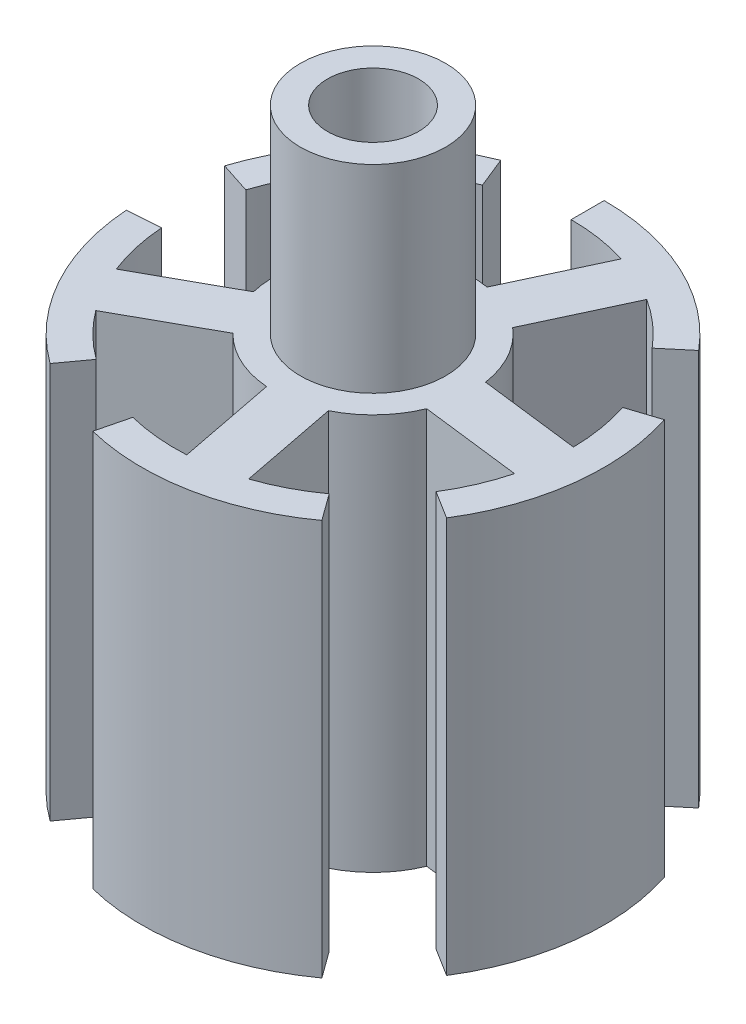
SolidWorks part; units mm, degrees
ref_plane "Front Plane" through (0, 0, 0) normal (0, 0, 1) x (1, 0, 0)
ref_plane "Top Plane" through (0, 0, 0) normal (0, 1, 0) x (1, 0, 0)
ref_plane "Right Plane" through (0, 0, 0) normal (1, 0, 0) x (0, 0, -1)
sketch "Sketch1" plane through (0, 0, 0) normal (0, 1, 0) x (1, 0, 0)
  line L0 (0, 17.5) -> (0, 15)
  line L1 (11.4907, 9.6418) -> (13.4058, 11.2488)
  line L2 (16.6435, 5.4078) -> (14.2658, 4.6353)
  line L3 (12.7207, -7.9488) -> (14.8408, -9.2736)
  line L4 (10.2862, -14.1578) -> (8.8168, -12.1353)
  line L5 (-3.6288, -14.5544) -> (-4.2336, -16.9802)
  line L6 (-10.2862, -14.1578) -> (-8.8168, -12.1353)
  line L7 (-14.9635, -1.0463) -> (-17.4574, -1.2207)
  line L8 (-16.6435, 5.4078) -> (-14.2658, 4.6353)
  line L9 (-5.6191, 13.9078) -> (-6.5556, 16.2257)
  arc A0 (0, 17.5) -> (13.4058, 11.2488) centre (0, 0) cw
  arc A1 (11.4907, 9.6418) -> (0, 15) centre (0, 0) ccw
  arc A2 (16.6435, 5.4078) -> (14.8408, -9.2736) centre (0, 0) cw
  arc A3 (12.7207, -7.9488) -> (14.2658, 4.6353) centre (0, 0) ccw
  arc A4 (10.2862, -14.1578) -> (-4.2336, -16.9802) centre (0, 0) cw
  arc A5 (-3.6288, -14.5544) -> (8.8168, -12.1353) centre (0, 0) ccw
  arc A6 (-10.2862, -14.1578) -> (-17.4574, -1.2207) centre (0, 0) cw
  arc A7 (-14.9635, -1.0463) -> (-8.8168, -12.1353) centre (0, 0) ccw
  arc A8 (-16.6435, 5.4078) -> (-6.5556, 16.2257) centre (0, 0) cw
  arc A9 (-5.6191, 13.9078) -> (-14.2658, 4.6353) centre (0, 0) ccw
  point P25 (0, 0)
  dimension "D1" = 5
extrude "Boss-Extrude2" add sketch "Sketch1" along normal blind 30
sketch "Sketch2" plane through (0, 0, 0) normal (0, 1, 0) x (1, 0, 0)
  line L0 (8.1519, 12.7494) -> (4.5267, 14.4399)
  line L1 (8.1519, 12.7494) -> (1.8723, -0.7172)
  line L2 (4.5267, 14.4399) -> (-1.7529, 0.9732)
  line L3 (1.8723, -0.7172) -> (-1.7529, 0.9732)
  line L4 (14.6445, -3.8131) -> (15.1319, 0.1571)
  line L5 (14.6445, -3.8131) -> (-0.1036, -2.0023)
  line L6 (15.1319, 0.1571) -> (0.3839, 1.9679)
  line L7 (-0.1036, -2.0023) -> (0.3839, 1.9679)
  line L8 (0.8989, -15.106) -> (4.8254, -14.3428)
  line L9 (0.8989, -15.106) -> (-1.9363, -0.5203)
  line L10 (4.8254, -14.3428) -> (1.9902, 0.243)
  line L11 (-1.9363, -0.5203) -> (1.9902, 0.243)
  line L12 (-14.0889, -5.5229) -> (-12.1497, -9.0214)
  line L13 (-14.0889, -5.5229) -> (-1.0931, 1.6808)
  line L14 (-12.1497, -9.0214) -> (0.8461, -1.8177)
  line L15 (-1.0931, 1.6808) -> (0.8461, -1.8177)
  line L16 (-9.6063, 11.6927) -> (-12.3343, 8.7673)
  line L17 (-9.6063, 11.6927) -> (1.2607, 1.559)
  line L18 (-12.3343, 8.7673) -> (-1.4673, -1.3664)
  line L19 (1.2607, 1.559) -> (-1.4673, -1.3664)
  arc A0 (11.4907, 9.6418) -> (0, 15) centre (0, 0) ccw construction
  point P8 (6.3393, 13.5946)
  point P27 (0, 0)
  dimension "D1" = 5
extrude "Boss-Extrude3" add sketch "Sketch2" along normal blind 30 contours L2 L17 L6 L1 L0 | L16 L18 L13 L2 L17 | L18 L13 L12 L14 L9 | L14 L9 L8 L10 L5 | L10 L5 L4 L6 L1 | L7 L15 L14 L5 L10 L1 L3 L11 | L19 L17 L6 L7 | L17 L19 L7 L3 L11 L10 L1 L6 | L19 L7 L6 L17 L2 L13 L15 L3 | L15 L13 L2 L3 | L11 L3 L1 L10 | L11 L19 L18 L9 L14 L5 L7 L15 | L19 L15 L3 L2 L13 L18 L9 L11 | L19 L11 L9 L18 | L15 L7 L5 L14 | L7 L6 L4 L5 | L2 L3 L1 L0 | L15 L14 L12 L13 region at (3.6821, 0, -7.8962) region at (8.6476, 0, 1.0618) region at (1.5876, 0, -0.88) region at (-0.3464, 0, -1.7818) region at (-6.3719, 0, -5.9419) region at (1.3275, 0, 1.2379) region at (1.4907, 0, 0.183) region at (0.6347, 0, -1.3612) region at (-1.0984, 0, -1.0243) region at (-1.8016, 0, -0.2212) region at (1.6624, 0, 8.5524) region at (-7.6201, 0, 4.2239) region at (-0.7671, 0, 1.6451) region at (0.2866, 0, 1.4743) region at (-1.3136, 0, 0.7281)
sketch "Sketch3" plane through (0, 0, 0) normal (0, 1, 0) x (1, 0, 0)
  circle A0 centre (0, 0) radius 7.5
extrude "Boss-Extrude4" add sketch "Sketch3" along normal blind 30
ref_plane "Plane2" through (0, 30, 0) normal (0, 1, 0) x (1, 0, 0)
sketch "Sketch5" plane through (0, 30, 0) normal (0, 1, 0) x (1, 0, 0)
  circle A0 centre (0, 0) radius 5.5
extrude "Boss-Extrude5" add sketch "Sketch5" along normal blind 15
sketch "Sketch4" plane through (0, 0, 0) normal (0, 1, 0) x (1, 0, 0)
  circle A0 centre (0, 0) radius 3.45
extrude "Cut-Extrude1" cut sketch "Sketch4" along normal through all
